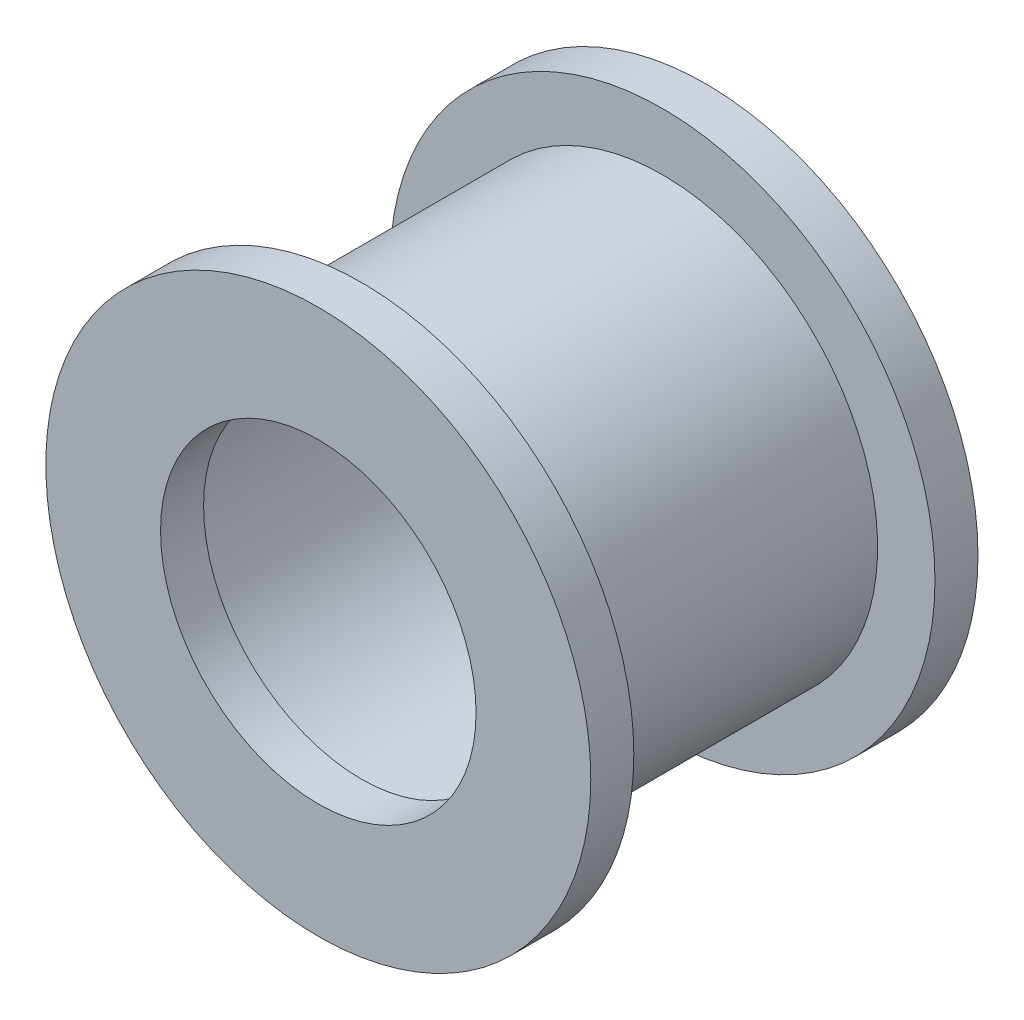
SolidWorks part; units mm, degrees
ref_plane "Plan de face" through (0, 0, 0) normal (0, 0, 1) x (1, 0, 0)
ref_plane "Plan de dessus" through (0, 0, 0) normal (0, 1, 0) x (1, 0, 0)
ref_plane "Plan de droite" through (0, 0, 0) normal (1, 0, 0) x (0, 0, -1)
sketch "Esquisse1" plane through (0, 0, 0) normal (0, 0, 1) x (1, 0, 0)
  circle A0 centre (0, 0) radius 5.5
  circle A1 centre (0, 0) radius 6.45
  circle A2 centre (0, 0) radius 9.5
  dimension "D1" = 11
  dimension "D2" = 12.9
  dimension "D3" = 19
extrude "Boss.-Extru.1" add sketch "Esquisse1" along normal blind 1.5 contours A1 A0 | A2 A1 region at (-6.2676, 0, 0) region at (-9.2313, 0, 0)
extrude "Boss.-Extru.4" add sketch "Esquisse1<3>" along normal blind 1.5 contours A1 A0 region at (-6.2676, 0, 0)
sketch "Esquisse1<3>" plane through (0, 0, 0) normal (0, 0, 1) x (1, 0, 0) same geometry as "Esquisse1"
sketch "Esquisse6" plane through (0, 0, 1.5) normal (0, 0, 1) x (1, 0, 0)
  circle A0 centre (0, 0) radius 7.5
  circle A1 centre (0, 0) radius 5.5
  circle A2 centre (0, 0) radius 6.5
extrude "Boss.-Extru.5" add sketch "Esquisse6" along normal blind 10.5 contours A0 A2 region at (-7.2879, 0, 1.5)
sketch "Esquisse7" plane through (0, 0, 12) normal (0, 0, 1) x (1, 0, 0)
  circle A0 centre (0, 0) radius 5.5
  circle A1 centre (0, 0) radius 6.5
  circle A2 centre (0, 0) radius 9.5
  circle A3 centre (0, 0) radius 7.5
  circle M1 centre (0, 0) radius 6.5
  circle M2 centre (0, 0) radius 7.5
extrude "Boss.-Extru.6" add sketch "Esquisse7" along normal blind 1.5 contours M2 M1 | A2 M2 | A0 M1 region at (-6.3162, 0, 12) region at (-9.2313, 0, 12) region at (-7.2879, 0, 12)
